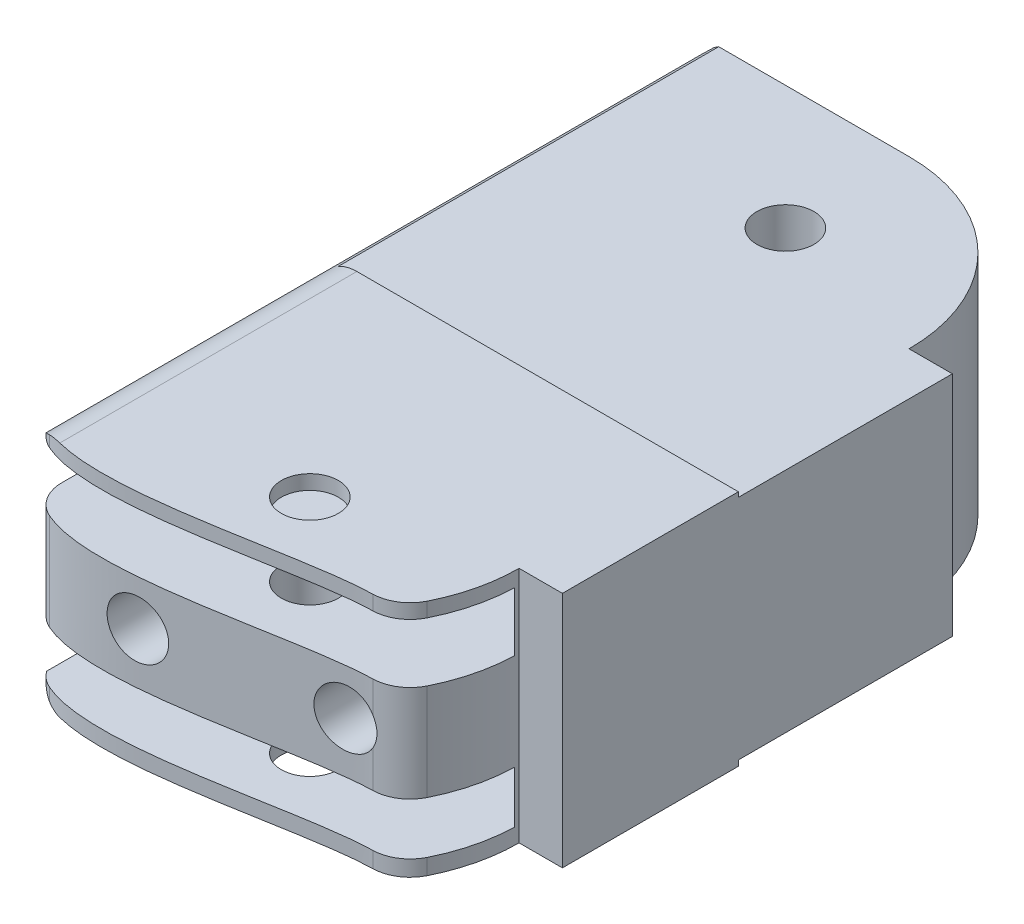
SolidWorks part; units mm, degrees
ref_plane "Front Plane" through (0, 0, 0) normal (0, 0, 1) x (1, 0, 0)
ref_plane "Top Plane" through (0, 0, 0) normal (0, 1, 0) x (1, 0, 0)
ref_plane "Right Plane" through (0, 0, 0) normal (1, 0, 0) x (0, 0, -1)
sketch "Sketch1" plane through (0, 0, 0) normal (0, 0, 1) x (1, 0, 0)
  line L0 (-24.2561, -24.0702) -> (-22.0061, -24.0702) construction
  line L1 (-24.2561, -17.8202) -> (-2.2017, -17.8202)
  line L2 (-24.2561, -17.8202) -> (-24.2561, -30.3202)
  line L3 (-24.2561, -30.3202) -> (-2.2017, -30.3202)
  line L4 (-2.2017, -17.8202) -> (-2.2017, -30.3202)
  line L5 (-2.2017, -24.0702) -> (-4.4517, -24.0702) construction
  line L6 (-22.0061, -24.0702) -> (-22.0061, -30.3202) construction
  line L7 (-4.4517, -24.0702) -> (-4.4517, -30.3202) construction
extrude "Boss-Extrude1" add sketch "Sketch1" along normal blind 40
sketch "Sketch2" plane through (0, -30.3202, 0) normal (0, -1, 0) x (1, 0, 0)
  line L0 (-4.4789, 29.25) -> (-2.2017, 29.25)
  line L1 (-24.2561, 0) -> (-2.2017, 0) construction
  line L2 (-13.2289, 0) -> (-13.2289, 8.75) construction
  line L4 (-24.2561, 40) -> (-24.2561, 0) construction
  line L5 (-4.4789, 8.75) -> (-2.2017, 8.75)
  line L6 (-2.2017, 40) -> (-2.2017, 0) construction
  line L7 (-13.2289, 40) -> (-13.2289, 29.25) construction
  line L8 (-24.2561, 40) -> (-2.2017, 40) construction
  line L10 (-13.2289, 29.25) -> (-13.2289, 31.5) construction
  line L11 (-13.2289, 8.75) -> (-13.2289, 6.5) construction
  line L12 (-24.2561, 0) -> (-2.2017, 0) construction
  arc A1 (-13.2289, 0) -> (-4.4789, 8.75) centre (-13.2289, 8.75) ccw
  circle A4 centre (-13.2289, 6.5) radius 1.5
  circle A5 centre (-13.2289, 31.5) radius 1.5
  arc A6 (-4.4789, 29.25) -> (-6.1039, 34.329) centre (-13.2289, 29.25) ccw
  spline S0 degree 3 poles (-2.2017, 8.75) (5.3921, 3.8803) (-0.7771, -4.5233) (-17.1743, -10.6233) (-34.8214, -0.026) (-24.2561, 8.75) knots 0 0 0 0 0.283273 0.504245 1 1 1 1
  spline S1 degree 3 poles (-24.2561, 29.25) (-34.2779, 38.4171) (-13.2275, 50.308) (7.8404, 38.417) (-2.2017, 29.25) knots 0 0 0 0 0.499862 1 1 1 1
  spline S2 degree 1 poles (-13.2289, 0) (-23.4906, 0) knots 0 0 1 1
  spline S3 degree 2 poles (-23.4906, 0) (-24.9665, 4.2378) (-24.2561, 8.75) knots 0 0 0 1 1 1
  spline S4 degree 3 poles (-6.1039, 34.329) (-10.7206, 33.5272) (-28.6414, 40.8452) (-24.2561, 29.25) knots 0 0 0 0 1 1 1 1
extrude "Cut-Extrude1" cut sketch "Sketch2" against normal blind 15 and the other way blind 10
fillet "Fillet3" radius 2 4 edges at (-24.2561, -17.8202, 18.7439) (-24.2561, -30.3202, 18.7439) (-24.2561, -24.0702, 3.0015) (-24.2561, -24.0702, 34.4864)
ref_plane "Plane1" through (0, 0, 0) normal (0, 0, 1) x (1, 0, 0)
sketch "Sketch5" plane through (0, 0, 0) normal (0, 0, 1) x (1, 0, 0)
  line L0 (-2.2017, -24.0702) -> (-8.4468, -24.0702) construction
  line L1 (-2.2017, -30.3202) -> (-24.2561, -30.3202) construction
  line L2 (-2.2017, -30.3202) -> (-2.2017, -17.8202) construction
  line L3 (-2.2017, -17.8202) -> (-24.2561, -17.8202) construction
  line L4 (-24.2561, -30.3202) -> (-24.2561, -17.8202) construction
  line L5 (-24.2561, -24.0702) -> (-18.0111, -24.0702) construction
  circle A0 centre (-18.0111, -24.0702) radius 1.5
  circle A1 centre (-8.4468, -24.0702) radius 1.5
extrude "Cut-Extrude4" cut sketch "Sketch5" along normal through all
ref_plane "Plane5" through (0, 0, 38) normal (0, 0, 1) x (1, 0, 0)
sketch "Sketch16" plane through (0, 0, 38) normal (0, 0, 1) x (1, 0, 0)
  line L0 (-2.1469, -17.3075) -> (-2.1469, -18.5832) construction
  line L1 (-2.1469, -17.3075) -> (-24.311, -17.3075) construction
  line L2 (-2.1469, -17.3075) -> (-2.1469, -30.7619) construction
  line L3 (-2.1469, -30.7619) -> (-24.311, -30.7619) construction
  line L4 (-24.311, -17.3075) -> (-24.311, -30.7619) construction
  line L5 (-2.1469, -17.3075) -> (-24.311, -30.7619) construction
  line L6 (-2.1469, -30.7619) -> (-24.311, -17.3075) construction
  line L7 (-2.1469, -30.7619) -> (-2.1316, -29.4863) construction
  line L8 (-13.2289, -21.681) -> (-13.2289, -24.0347) construction
  line L9 (-2.1469, -18.5832) -> (-24.311, -18.5832)
  line L10 (-2.1469, -18.5832) -> (-2.1469, -21.681)
  line L11 (-2.1469, -21.681) -> (-24.311, -21.681)
  line L12 (-24.311, -18.5832) -> (-24.311, -21.681)
  line L13 (-2.1469, -18.5832) -> (-24.311, -21.681) construction
  line L14 (-2.1469, -21.681) -> (-24.311, -18.5832) construction
  line L15 (-2.1316, -29.4863) -> (-24.3262, -29.4863)
  line L16 (-2.1316, -29.4863) -> (-2.1316, -26.7619)
  line L17 (-2.1316, -26.7619) -> (-24.3262, -26.7619)
  line L18 (-24.3262, -29.4863) -> (-24.3262, -26.7619)
  line L19 (-2.1316, -29.4863) -> (-24.3262, -26.7619) construction
  line L20 (-2.1316, -26.7619) -> (-24.3262, -29.4863) construction
  line L21 (-13.2289, -24.0347) -> (-13.2289, -26.7619) construction
  point P4 (-13.2289, -24.0347)
  point P10 (-13.2289, -20.1321)
  point P14 (-13.2289, -28.1241)
extrude "Cut-Extrude6" cut sketch "Sketch16" against normal blind 8.5
fillet "Fillet4" radius 2 3 edges at (-6.1039, -18.2017, 34.329) (-6.1039, -24.2214, 34.329) (-6.1039, -29.9032, 34.329)
sketch "Sketch17" plane through (0, 0, 29.5) normal (0, 0, 1) x (1, 0, 0)
  line L0 (-24.2561, -21.681) -> (-4.4825, -21.681) construction
  line L1 (-4.4825, -18.5832) -> (-22.3385, -18.5832)
  line L2 (-4.4825, -18.5832) -> (-4.4825, -21.681)
  line L3 (-4.4825, -21.681) -> (-22.3385, -21.681)
  line L4 (-22.3385, -18.5832) -> (-22.3385, -21.681)
  line L5 (-4.4825, -18.5832) -> (-22.3385, -21.681) construction
  line L6 (-4.4825, -21.681) -> (-22.3385, -18.5832) construction
  line L7 (-23.881, -29.4863) -> (-4.4825, -29.4863) construction
  line L8 (-4.4825, -26.7619) -> (-22.3385, -26.7619)
  line L9 (-4.4825, -26.7619) -> (-4.4825, -29.4863)
  line L10 (-4.4825, -29.4863) -> (-22.3385, -29.4863)
  line L11 (-22.3385, -26.7619) -> (-22.3385, -29.4863)
  line L12 (-4.4825, -26.7619) -> (-22.3385, -29.4863) construction
  line L13 (-4.4825, -29.4863) -> (-22.3385, -26.7619) construction
  point P4 (-13.4105, -20.1321)
  point P12 (-13.4105, -28.1241)
extrude "Cut-Extrude7" cut sketch "Sketch17" against normal blind 5
sketch "Sketch18" plane through (0, 0, 0) normal (0, 0, 1) x (1, 0, 0)
  line L1 (-25.0892, -17.3162) -> (-1.3306, -17.3162)
  line L2 (-25.0892, -17.3162) -> (-25.0892, -18.0755)
  line L3 (-25.0892, -18.0755) -> (-1.3306, -18.0755)
  line L4 (-1.3306, -17.3162) -> (-1.3306, -18.0755)
  line L5 (-25.0892, -17.3162) -> (-1.3306, -18.0755) construction
  line L6 (-25.0892, -18.0755) -> (-1.3306, -17.3162) construction
  line L7 (-25.0484, -30.032) -> (-1.3306, -30.032)
  line L8 (-25.0484, -30.032) -> (-25.0484, -30.7603)
  line L9 (-25.0484, -30.7603) -> (-1.3306, -30.7603)
  line L10 (-1.3306, -30.032) -> (-1.3306, -30.7603)
  line L11 (-25.0484, -30.032) -> (-1.3306, -30.7603) construction
  line L12 (-25.0484, -30.7603) -> (-1.3306, -30.032) construction
  point P4 (-13.2099, -17.6959)
  point P9 (-13.1895, -30.3961)
  point P10 (-25.0484, -30.032)
extrude "Cut-Extrude8" cut sketch "Sketch18" along normal blind 20
